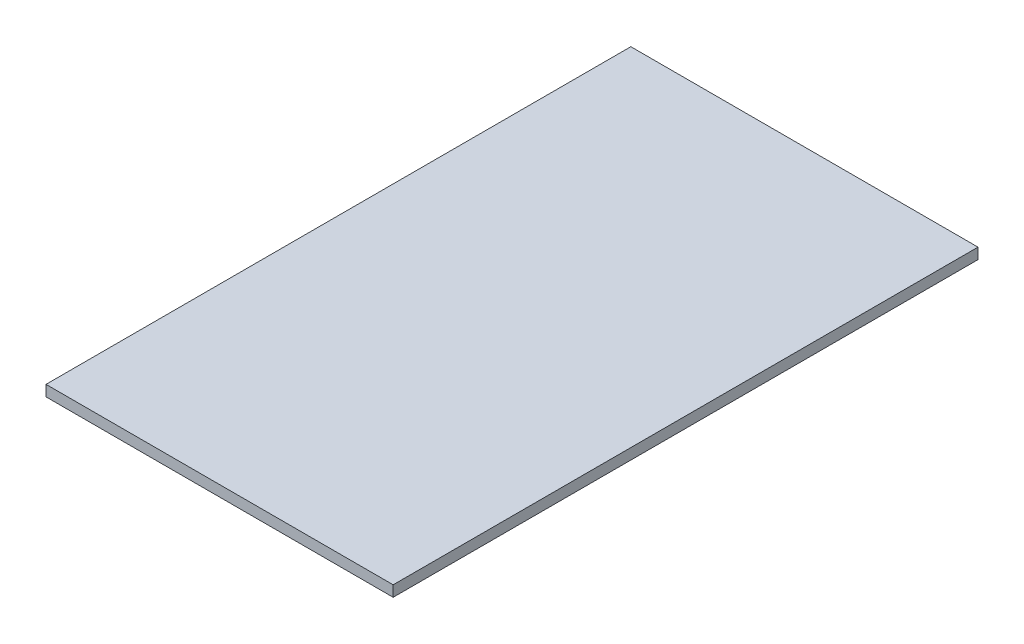
SolidWorks part; units mm, degrees
material "Balsa"
ref_plane "Front Plane" through (0, 0, 0) normal (0, 0, 1) x (1, 0, 0)
ref_plane "Top Plane" through (0, 0, 0) normal (0, 1, 0) x (1, 0, 0)
ref_plane "Right Plane" through (0, 0, 0) normal (1, 0, 0) x (0, 0, -1)
sketch "Sketch1" plane through (0, 0, 0) normal (0, 1, 0) x (1, 0, 0)
  line L0 (-152.4, 304.8) -> (152.4, 304.8) construction
  line L1 (152.4, 304.8) -> (152.4, -304.8) construction
  line L2 (0, 304.8) -> (0, 0) construction
  line L3 (0, 0) -> (152.4, 0) construction
  dimension "Width" = 304.8
  dimension "Length" = 609.6
sketch "Sketch2" plane through (0, 0, 0) normal (1, 0, 0) x (0, 0, -1)
  line L0 (304.8, 0) -> (304.8, -9.525) construction
  dimension "Thk" = 9.525
sketch "Sketch3" plane through (0, 0, 0) normal (0, 1, 0) x (1, 0, 0)
  line L1 (-152.4, 304.8) -> (152.4, 304.8)
  line L2 (-152.4, 304.8) -> (-152.4, -304.8)
  line L3 (-152.4, -304.8) -> (152.4, -304.8)
  line L4 (152.4, 304.8) -> (152.4, -304.8)
extrude "Boss-Extrude1" add sketch "Sketch3" against normal up to vertex (9.525 mm away) up to point (0, -9.525, -304.8)
sketch "Sketch4" plane through (0, 0, 0) normal (0, 1, 0) x (1, 0, 0)
  line L0 (152.4, -304.8) -> (152.4, 304.8) construction
  line L1 (-152.4, 304.8) -> (152.4, 304.8)
  line L2 (-152.4, 304.8) -> (-152.4, 208.661)
  line L3 (-152.4, 208.661) -> (152.4, 208.661)
  line L4 (152.4, 304.8) -> (152.4, 208.661)
  line L5 (-152.4, -304.8) -> (152.4, -304.8) construction
  dimension "D1" = 513.461
extrude "Cut-Extrude1" cut sketch "Sketch4" against normal blind 15.24 contours L2 L1 L4 L3
